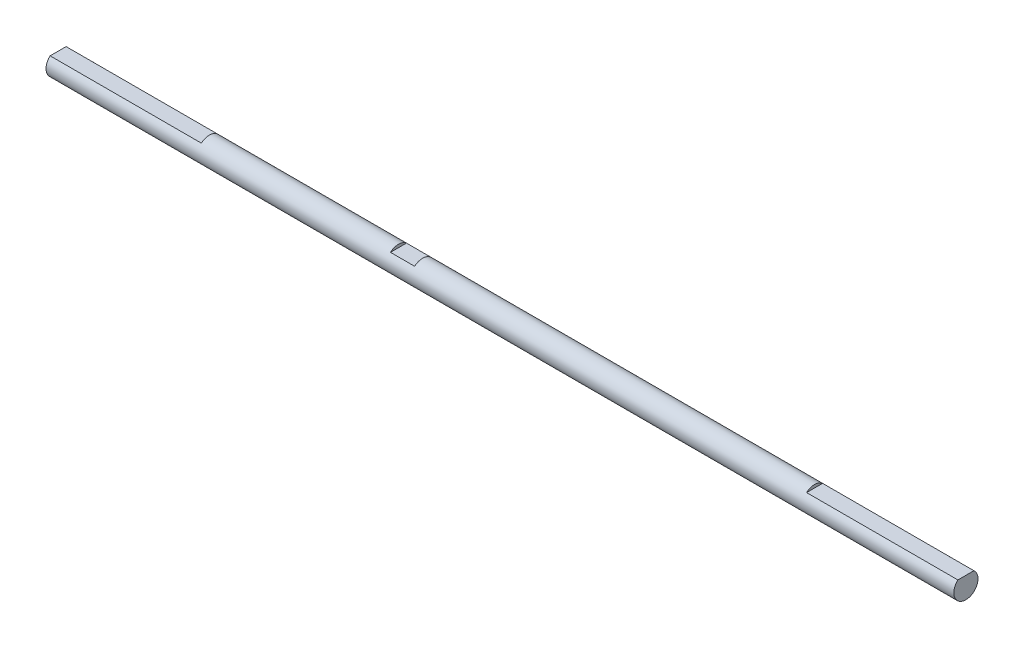
SolidWorks part; units mm, degrees
ref_plane "Front Plane" through (0, 0, 0) normal (0, 0, 1) x (1, 0, 0)
ref_plane "Top Plane" through (0, 0, 0) normal (0, 1, 0) x (1, 0, 0)
ref_plane "Right Plane" through (0, 0, 0) normal (1, 0, 0) x (0, 0, -1)
sketch "Sketch1" plane through (0, 0, 0) normal (1, 0, 0) x (0, 0, -1)
  line L0 (-1.3229, 1.5) -> (1.3229, 1.5)
  arc A0 (-1.3229, 1.5) -> (1.3229, 1.5) centre (0, 0) ccw
  dimension "D1" = 4
  dimension "D2" = 1.5
extrude "Boss-Extrude1" add sketch "Sketch1" along normal mid plane 150
sketch "Sketch2" plane through (0, 0, 0) normal (1, 0, 0) x (0, 0, -1)
  circle A0 centre (0, 0) radius 2
  arc A1 (-1.3229, 1.5) -> (1.3229, 1.5) centre (0, 0) ccw construction
extrude "Boss-Extrude2" add sketch "Sketch2" along normal mid plane 100
sketch "Sketch3" plane through (0, 0, 0) normal (0, 0, 1) x (1, 0, 0)
  line L0 (50, 2) -> (-50, 2) construction
  line L1 (-18.76, 2) -> (-14.76, 2)
  line L2 (-18.76, 2) -> (-18.76, 1.5)
  line L3 (-18.76, 1.5) -> (-14.76, 1.5)
  line L4 (-14.76, 2) -> (-14.76, 1.5)
  line L5 (-50, 1.5) -> (-75, 1.5) construction
  point P8 (-10.1401, 1.5)
  dimension "D1" = 4
  dimension "D2" = 14.76
extrude "Cut-Extrude1" cut sketch "Sketch3" against normal through all both and the other way through all
